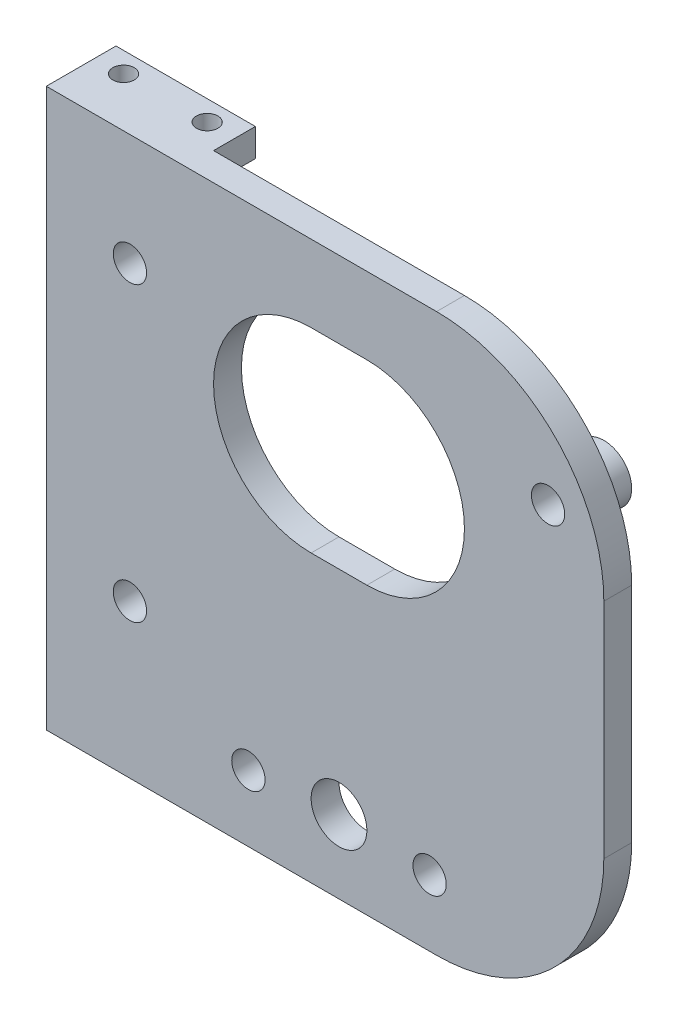
SolidWorks part; units mm, degrees
material "Polycarbonate"
ref_plane "Front Plane" through (0, 0, 0) normal (0, 0, 1) x (1, 0, 0)
ref_plane "Top Plane" through (0, 0, 0) normal (0, 1, 0) x (1, 0, 0)
ref_plane "Right Plane" through (0, 0, 0) normal (1, 0, 0) x (0, 0, -1)
sketch "Sketch1" plane through (0, 0, 0) normal (0, 0, 1) x (1, 0, 0)
  line L1 (-31.75, 31.75) -> (31.75, 31.75)
  line L2 (-31.75, 31.75) -> (-31.75, -31.75)
  line L3 (-31.75, -31.75) -> (31.75, -31.75)
  line L4 (31.75, 31.75) -> (31.75, -31.75)
  line L5 (-31.75, 31.75) -> (31.75, -31.75) construction
  line L6 (-31.75, -31.75) -> (31.75, 31.75) construction
  point P0 (0, 0)
  dimension "D1" = 63.5
  dimension "D2" = 63.5
extrude "Boss-Extrude1" add sketch "Sketch1" along normal blind 3.175
sketch "Sketch2" plane through (0, 0, 0) normal (0, 0, -1) x (-1, 0, 0)
  line L0 (31.75, -31.75) -> (-31.75, -31.75) construction
  line L1 (15.875, -31.75) -> (25.4, -31.75)
  line L2 (15.875, -31.75) -> (15.875, -28.595)
  line L3 (15.875, -28.595) -> (25.7558, -28.595)
  line L8 (31.75, -31.75) -> (25.4, -31.75)
  line L9 (31.75, -31.75) -> (31.75, -28.595)
  line L10 (31.75, -28.595) -> (25.7558, -28.595)
  dimension "D1" = 3.175
  dimension "D2" = 15.875
extrude "Boss-Extrude2" add sketch "Sketch2" along normal blind 4.7625
hole_wizard "#2 Clearance Hole2" positions "Sketch5" profile "Sketch6" hole size "#2" standard "ANSI Inch" end condition up to next
sketch "Sketch5" plane through (0, -28.595, 0) normal (0, 1, 0) x (1, 0, 0)
  line L0 (-31.75, 4.7625) -> (-31.75, 0) construction
  line L1 (-15.875, 4.7625) -> (-15.875, 0) construction
  point P0 (-28.575, 2.4476)
  point P2 (-19.05, 2.4476)
  dimension "D1" = 3.175
  dimension "D2" = 3.175
sketch "Sketch6" plane through (-28.575, -28.595, -2.4476) normal (1, 0, 0) x (0, 0, 1)
  line L0 (0, 0) -> (0, 3.155)
  line L1 (0, 3.155) -> (1.2192, 3.155)
  line L2 (1.2192, 3.155) -> (1.2192, 0)
  line L5 (1.2192, 0) -> (0, 0)
  line L11 (0, -6.35) -> (0, 107.95) construction
  dimension "Thru Hole Dia." = 2.4384
  dimension "Thru Hole Depth" = 3.155
fillet "Fillet1" radius 19.05 2 edges at (31.75, 31.75, 1.5875) (31.75, -31.75, 1.5875)
sketch "Sketch7" plane through (0, 0, 0) normal (0, 0, -1) x (-1, 0, 0)
  line L0 (15.875, -28.595) -> (15.875, -31.75) construction
  line L1 (31.75, 31.75) -> (15.875, 31.75)
  line L2 (31.75, 31.75) -> (31.75, 28.575)
  line L3 (31.75, 28.575) -> (15.875, 28.575)
  line L4 (15.875, 31.75) -> (15.875, 28.575)
  dimension "D1" = 3.175
extrude "Boss-Extrude3" add sketch "Sketch7" along normal blind 4.7625
hole_wizard "#2 Clearance Hole3" positions "Sketch8" profile "Sketch9" hole size "#2" standard "ANSI Inch" end condition up to next
sketch "Sketch8" plane through (0, 31.75, 0) normal (0, 1, 0) x (1, 0, 0)
  line L0 (12.7, -3.175) -> (-31.75, -3.175) construction
  line L1 (-31.75, -3.175) -> (-31.75, 4.7625) construction
  line L2 (-15.875, 4.7625) -> (-15.875, 0) construction
  point P0 (-28.575, 2.4476)
  point P3 (-19.05, 2.4476)
  dimension "D1" = 5.6226
  dimension "D2" = 3.175
  dimension "D3" = 5.6226
  dimension "D4" = 3.175
sketch "Sketch9" plane through (-28.575, 31.75, -2.4476) normal (1, 0, 0) x (0, 0, 1)
  line L0 (0, 0) -> (0, 3.175)
  line L1 (0, 3.175) -> (1.2192, 3.175)
  line L2 (1.2192, 3.175) -> (1.2192, 0)
  line L5 (1.2192, 0) -> (0, 0)
  line L11 (0, -6.35) -> (0, 107.95) construction
  dimension "Thru Hole Dia." = 2.4384
  dimension "Thru Hole Depth" = 3.175
sketch "Sketch10" plane through (0, 0, 3.175) normal (0, 0, 1) x (1, 0, 0)
  line L0 (-22.225, 19.05) -> (-22.225, -14.2875) construction
  line L1 (-22.225, -14.2875) -> (-8.7313, -24.2094) construction
  line L2 (-8.7313, -24.2094) -> (11.9062, -24.2094) construction
  line L3 (11.9062, -24.2094) -> (25.4, -24.2094) construction
  line L4 (25.4, -24.2094) -> (25.4, 19.05) construction
  line L5 (25.4, 19.05) -> (-22.225, 19.05) construction
  line L6 (-31.75, 31.75) -> (-31.75, -31.75) construction
  line L7 (12.7, 31.75) -> (-31.75, 31.75) construction
  circle A0 centre (25.4, 19.05) radius 3.175
  circle A1 centre (-22.225, 19.05) radius 3.175
  circle A2 centre (-22.225, -14.2875) radius 3.175
  circle A3 centre (-8.7313, -24.2094) radius 3.175
  circle A4 centre (11.9062, -24.2094) radius 3.175
  dimension "D1" = 6.35
  dimension "D2" = 9.525
  dimension "D3" = 47.625
  dimension "D4" = 43.2594
  dimension "D5" = 13.4938
  dimension "D6" = 20.6375
  dimension "D7" = 33.3375
  dimension "D8" = 12.7
extrude "Boss-Extrude4" add sketch "Sketch10" against normal blind 3.175 from surface starting at face at (-3.0209, -0.004, 0)
hole_wizard "#6 Clearance Hole1" positions "Sketch11" profile "Sketch12" hole size "#6" standard "ANSI Inch" end condition through all
sketch "Sketch11" plane through (0, 0, -3.175) normal (0, 0, -1) x (-1, 0, 0)
  point P0 (-25.4, 19.05)
  point P3 (22.225, 19.05)
  point P6 (22.225, -14.2875)
  point P9 (8.7313, -24.2094)
  point P12 (-11.9062, -24.2094)
sketch "Sketch12" plane through (25.4, 19.05, -3.175) normal (1, 0, 0) x (0, 1, 0)
  line L0 (0, 0) -> (0, 6.35)
  line L1 (0, 6.35) -> (1.8986, 6.35)
  line L2 (1.8986, 6.35) -> (1.8986, 0)
  line L5 (1.8986, 0) -> (0, 0)
  line L11 (0, -6.35) -> (0, 107.95) construction
  dimension "Thru Hole Dia." = 3.7973
  dimension "Thru Hole Depth" = 6.35
sketch "Sketch13" plane through (0, 0, 3.175) normal (0, 0, 1) x (1, 0, 0)
  line L0 (-22.225, 19.05) -> (25.4, 19.05) construction
  line L1 (12.7, 31.75) -> (-31.75, 31.75) construction
  line L2 (-12.7, 0.7938) -> (15.875, 0.7938) construction
  line L3 (-12.7, 0.7938) -> (-12.7, 23.0188) construction
  line L4 (-12.7, 23.0188) -> (15.875, 23.0188) construction
  line L5 (15.875, 0.7938) -> (15.875, 23.0188) construction
  line L6 (-1.5875, 11.9063) -> (4.7625, 11.9063) construction
  line L7 (-1.5875, 23.0188) -> (4.7625, 23.0188)
  line L8 (-1.5875, 0.7938) -> (4.7625, 0.7938)
  arc A0 (-1.5875, 23.0188) -> (-1.5875, 0.7938) centre (-1.5875, 11.9063) ccw
  arc A1 (4.7625, 0.7938) -> (4.7625, 23.0188) centre (4.7625, 11.9063) ccw
  circle A2 centre (1.5875, -23.4156) radius 3.175
  circle A4 centre (-8.7313, -24.2094) radius 1.8986 construction
  point P8 (1.5875, 23.0188)
  point P9 (1.5875, 19.05)
  point P14 (1.5875, 11.9063)
  dimension "D4" = 6.35
  dimension "D1" = 8.7312
  dimension "D2" = 28.575
  dimension "D3" = 22.225
  dimension "D5" = 0.7937
extrude "Cut-Extrude1" cut sketch "Sketch13" against normal blind 3.175
